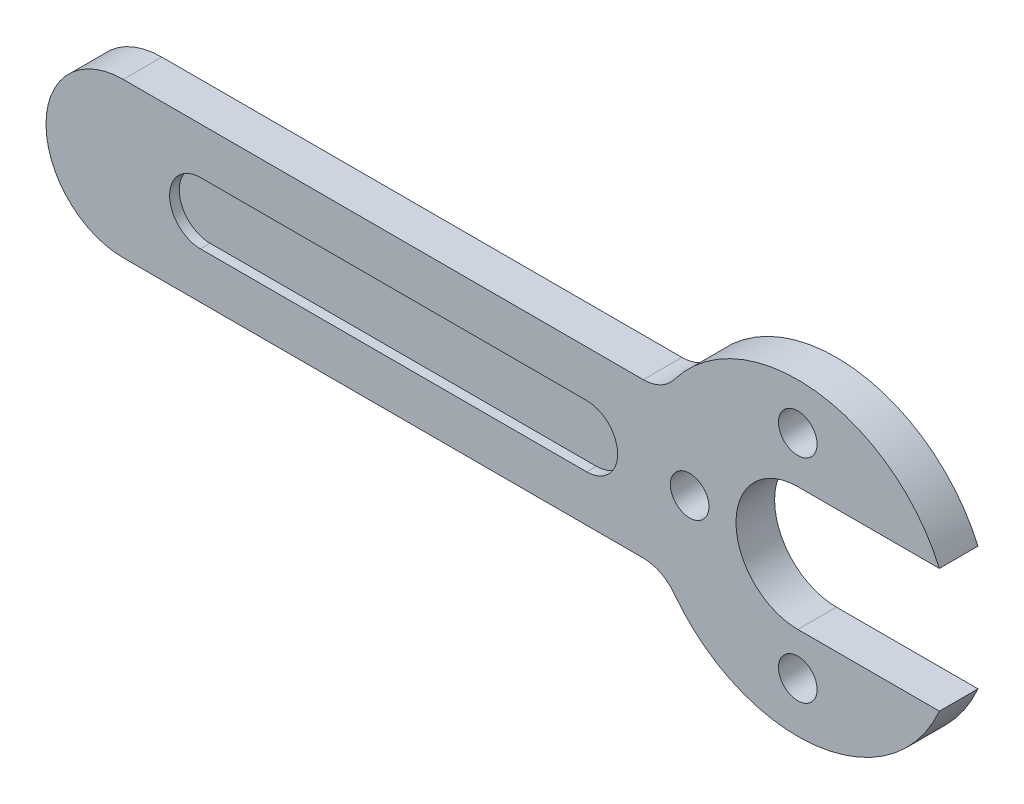
SolidWorks part; units mm, degrees
ref_plane "Front Plane" through (0, 0, 0) normal (0, 0, 1) x (1, 0, 0)
ref_plane "Top Plane" through (0, 0, 0) normal (0, 1, 0) x (1, 0, 0)
ref_plane "Right Plane" through (0, 0, 0) normal (1, 0, 0) x (0, 0, -1)
sketch "Sketch1" plane through (0, 0, 0) normal (0, 0, 1) x (1, 0, 0)
  line L0 (0, 16) -> (36.6606, 16)
  line L1 (0, -16) -> (36.6606, -16)
  line L2 (-54.641, 0) -> (36.6606, 0) construction
  line L3 (0, 47.2558) -> (0, -52.4822) construction
  line L4 (-40, 20) -> (-174.641, 20)
  line L5 (-174.641, -20) -> (-40, -20)
  line L6 (-54.641, 0) -> (-154.641, 0) construction
  line L7 (-154.641, 0) -> (-54.641, 0) construction
  line L8 (-154.641, 8) -> (-54.641, 8)
  line L9 (-154.641, -8) -> (-54.641, -8)
  arc A0 (36.6606, 16) -> (-32, 24) centre (0, 0) ccw
  arc A1 (0, 16) -> (0, -16) centre (0, 0) ccw
  circle A2 centre (0, 28) radius 5
  circle A3 centre (0, -27) radius 5
  circle A4 centre (-28, 0) radius 5
  circle A5 centre (0, 0) radius 28 construction
  arc A6 (-174.641, 20) -> (-174.641, -20) centre (-174.641, 0) ccw
  arc A7 (-32, -24) -> (36.6606, -16) centre (0, 0) ccw
  arc A8 (-40, -20) -> (-32, -24) centre (-40, -30) cw
  arc A9 (-40, 20) -> (-32, 24) centre (-40, 30) ccw
  arc A10 (-154.641, 8) -> (-154.641, -8) centre (-154.641, 0) ccw
  arc A11 (-54.641, -8) -> (-54.641, 8) centre (-54.641, 0) ccw
  point P20 (-104.641, 0)
  point P28 (-34.641, -20)
  point P31 (-34.641, 20)
  point P39 (-104.641, 0)
  dimension "D1" = 80
  dimension "D2" = 32
  dimension "D3" = 10
  dimension "D4" = 28
  dimension "D5" = 55
  dimension "D6" = 20
  dimension "D8" = 10
  dimension "D10" = 8
  dimension "D7" = 140
  dimension "D9" = 100
  dimension "D11" = 20
extrude "Boss-Extrude1" add sketch "Sketch1" along normal mid plane 10
extrude "Boss-Extrude2" add sketch "Sketch1<2>" along normal mid plane 5 contours L9 A11 L8 A10 region at (-104.641, 0, 0)
sketch "Sketch1<2>" plane through (0, 0, 0) normal (0, 0, 1) x (1, 0, 0) same geometry as "Sketch1"
